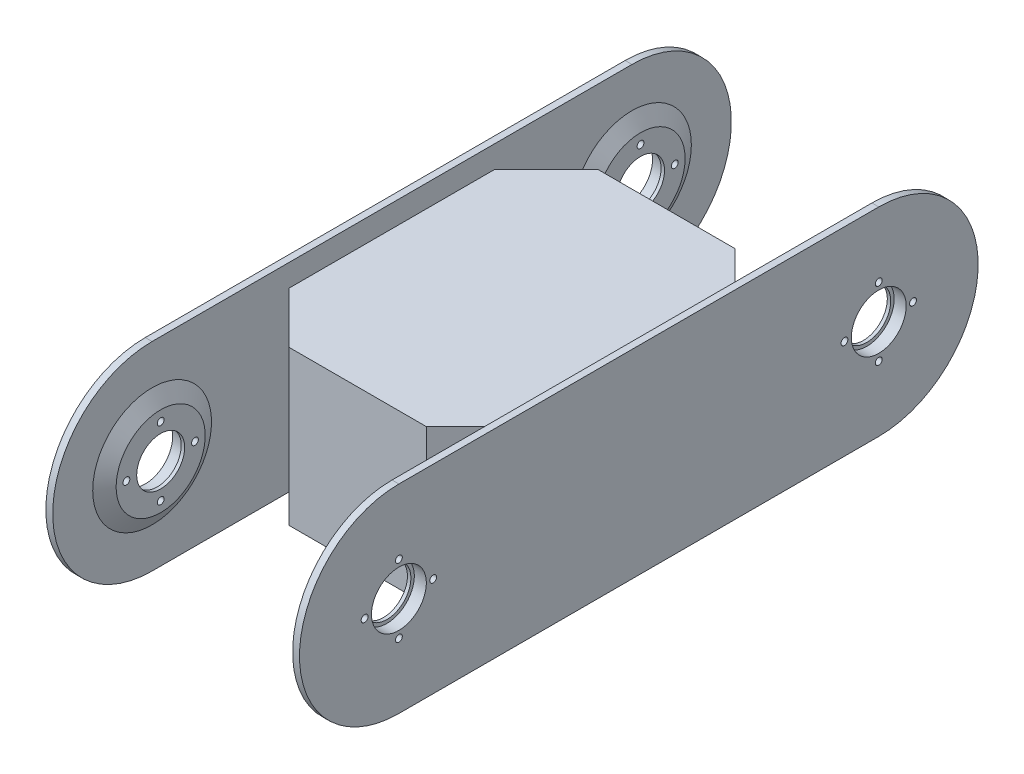
SolidWorks part; units mm, degrees
ref_plane "Front Plane" through (0, 0, 0) normal (0, 0, 1) x (1, 0, 0)
ref_plane "Top Plane" through (0, 0, 0) normal (0, 1, 0) x (1, 0, 0)
ref_plane "Right Plane" through (0, 0, 0) normal (1, 0, 0) x (0, 0, -1)
sketch "Sketch1" plane through (0, 0, 0) normal (0, 1, 0) x (1, 0, 0)
  line L1 (-70, -90) -> (70, -90)
  line L2 (-70, -90) -> (-70, 90)
  line L3 (-70, 90) -> (70, 90)
  line L4 (70, -90) -> (70, 90)
  line L5 (-70, -90) -> (70, 90) construction
  line L6 (-70, 90) -> (70, -90) construction
  point P0 (0, 0)
  dimension "D1" = 140
  dimension "D2" = 180
extrude "Boss-Extrude1" add sketch "Sketch1" along normal blind 90 contours L3 L4 L1 L2
chamfer "Chamfer1" distance 30 angle 45 4 edges at (-70, 45, -90) (70, 45, -90) (-70, 45, 90) (70, 45, 90)
sketch "Sketch2" plane through (70, 0, 0) normal (1, 0, 0) x (0, 0, -1)
  line L0 (90, 45) -> (-90, 45) construction
  line L1 (90, 90) -> (90, 0) construction
  line L2 (-90, 90) -> (-90, 0) construction
  line L3 (-140, 45) -> (140, 45) construction
  line L4 (-140, 103) -> (140, 103)
  line L5 (-140, -13) -> (140, -13)
  arc A0 (-140, 103) -> (-140, -13) centre (-140, 45) ccw
  arc A1 (140, -13) -> (140, 103) centre (140, 45) ccw
  point P8 (0, 45)
  dimension "D2" = 58
  dimension "D1" = 280
extrude "Boss-Extrude2" add sketch "Sketch2" along normal blind 4
ref_plane "Plane1" through (65, 0, 0) normal (-1, 0, 0) x (0, 0, 1)
sketch "Sketch3" plane through (65, 0, 0) normal (-1, 0, 0) x (0, 0, 1)
  circle A0 centre (140, 45) radius 16
  circle A1 centre (140, 45) radius 26
  dimension "D1" = 32
  dimension "D2" = 52
extrude "Boss-Extrude3" add sketch "Sketch3" against normal up to surface (5 mm away) draft 60 contours A1 up to face at (70, 45, 0) draft outward yes
sketch "Sketch4" plane through (65, 0, 0) normal (-1, 0, 0) x (0, 0, 1)
  circle A0 centre (140, 45) radius 14
  dimension "D1" = 28
extrude "Cut-Extrude1" cut sketch "Sketch4" against normal blind 2
sketch "Sketch5" plane through (67, 0, 0) normal (-1, 0, 0) x (0, 0, 1)
  circle A0 centre (140, 45) radius 16
  dimension "D1" = 32
extrude "Cut-Extrude2" cut sketch "Sketch5" against normal through all
mirror "Mirror1" about plane through (0, 0, 0) normal (0, 0, 1) of "Cut-Extrude2", "Cut-Extrude1", "Boss-Extrude3"
mirror "Mirror2" about plane through (0, 0, 0) normal (1, 0, 0) of "Mirror1", "Cut-Extrude2", "Cut-Extrude1", "Boss-Extrude3", "Boss-Extrude2"
sketch "Sketch6" plane through (-65, 0, 0) normal (1, 0, 0) x (0, 0, -1)
  line L0 (-140, 45) -> (-140, 65) construction
  circle A0 centre (-140, 45) radius 16 construction
  circle A1 centre (-140, 45) radius 16 construction
  circle A2 centre (-140, 65) radius 2
  circle A3 centre (-120, 45) radius 2
  circle A4 centre (-140, 25) radius 2
  circle A5 centre (-160, 45) radius 2
  point P6 (-160.2583, 48.3246)
  point P7 (-140, 45)
  point P13 (-140, 45)
  dimension "D1" = 4
  dimension "D2" = 20
  dimension "D3" = 4
extrude "Cut-Extrude3" cut sketch "Sketch6" against normal through all and the other way through all
mirror "Mirror3" about plane through (0, 0, 0) normal (0, 0, 1) of "Cut-Extrude3"
